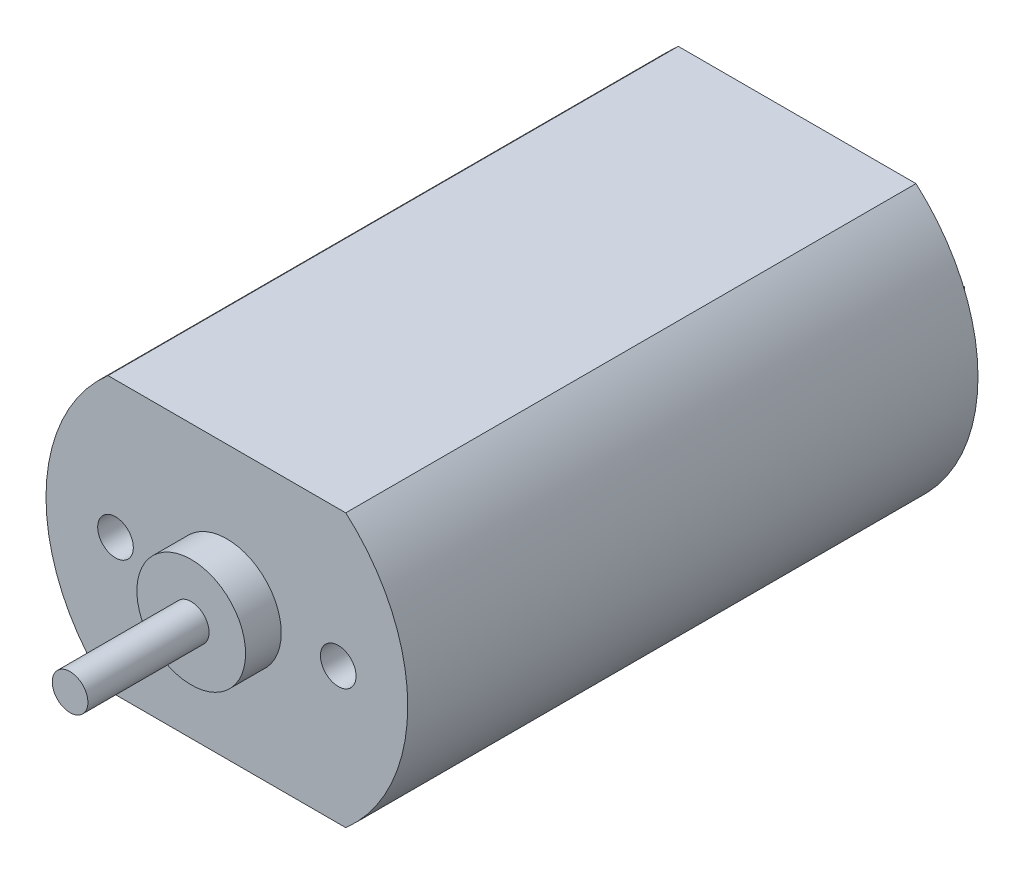
SolidWorks part; units mm, degrees
ref_plane "前视基准面" through (0, 0, 0) normal (0, 0, 1) x (1, 0, 0)
ref_plane "上视基准面" through (0, 0, 0) normal (0, 1, 0) x (1, 0, 0)
ref_plane "右视基准面" through (0, 0, 0) normal (1, 0, 0) x (0, 0, -1)
other "Configuration Table"
sketch "草图1" plane through (0, 0, 0) normal (0, 0, 1) x (1, 0, 0)
  circle A0 centre (0, 0) radius 10.15
  dimension "D1" = 20.3
extrude "凸台-拉伸1" add sketch "草图1" along normal blind 32
sketch "草图3" plane through (0, 0, 32) normal (0, 0, 1) x (1, 0, 0)
  line L1 (-6.6708, -7.65) -> (6.6708, -7.65)
  line L2 (-6.6708, -7.65) -> (-6.6708, 7.65)
  line L3 (-6.6708, 7.65) -> (6.6708, 7.65)
  line L4 (6.6708, -7.65) -> (6.6708, 7.65)
  line L5 (-6.6708, -7.65) -> (6.6708, 7.65) construction
  line L6 (-6.6708, 7.65) -> (6.6708, -7.65) construction
  circle A0 centre (0, 0) radius 10.15
  circle M3 centre (0, 0) radius 10.15
  dimension "D1" = 20.3
  dimension "D2" = 15.3
extrude "切除-拉伸1" cut sketch "草图3" against normal through all contours L3 M3 | L1 M3 region at (0, -8.6614, 32) region at (0, 8.6614, 32)
sketch "草图4" plane through (0, 0, 0) normal (0, 0, -1) x (-1, 0, 0)
  line L0 (6.4, -1) -> (6.4, 1)
  line L1 (-6.4, 1) -> (-6, 1)
  line L2 (-6.4, 1) -> (-6.4, -1)
  line L3 (-6.4, -1) -> (-6, -1)
  line L4 (-6, 1) -> (-6, -1)
  line L5 (-6.4, 1) -> (-6, -1) construction
  line L6 (-6.4, -1) -> (-6, 1) construction
  line L7 (6.4, -1) -> (6, -1)
  line L8 (6, -1) -> (6, 1)
  line L9 (6.4, 1) -> (6, 1)
  point P0 (-6.2, 0)
  point P13 (0, 0)
  dimension "D1" = 0.4
  dimension "D2" = 2
  dimension "D3" = 6
  dimension "D4" = 1
  dimension "D6" = 0.4
  dimension "D7" = 2
  dimension "D8" = 6
  dimension "D9" = 1
  dimension "D5" = 2
extrude "凸台-拉伸2" add sketch "草图4" along normal blind 3
sketch "草图6" plane through (0, 0, 32) normal (0, 0, 1) x (1, 0, 0)
  circle A0 centre (0, 0) radius 3.05
  circle A1 centre (-6.25, 0) radius 1
  circle A2 centre (6.25, 0) radius 1
  dimension "D1" = 2
  dimension "D2" = 2
  dimension "D5" = 6.1
  dimension "D3" = 6.25
  dimension "D4" = 6.25
extrude "切除-拉伸2" cut sketch "草图6" against normal blind 4 contours A1 | A2 region at (-6.25, 0, 32) region at (6.25, 0, 32)
extrude "凸台-拉伸3" add sketch "草图6<4>" along normal blind 2 contours A0 region at (0, 0, 32)
sketch "草图6<4>" plane through (0, 0, 32) normal (0, 0, 1) x (1, 0, 0) same geometry as "草图6"
sketch "草图7" plane through (0, 0, 34) normal (0, 0, 1) x (1, 0, 0)
  circle A0 centre (0, 0) radius 1
  dimension "D1" = 2
extrude "凸台-拉伸4" add sketch "草图7" along normal blind 6.8
